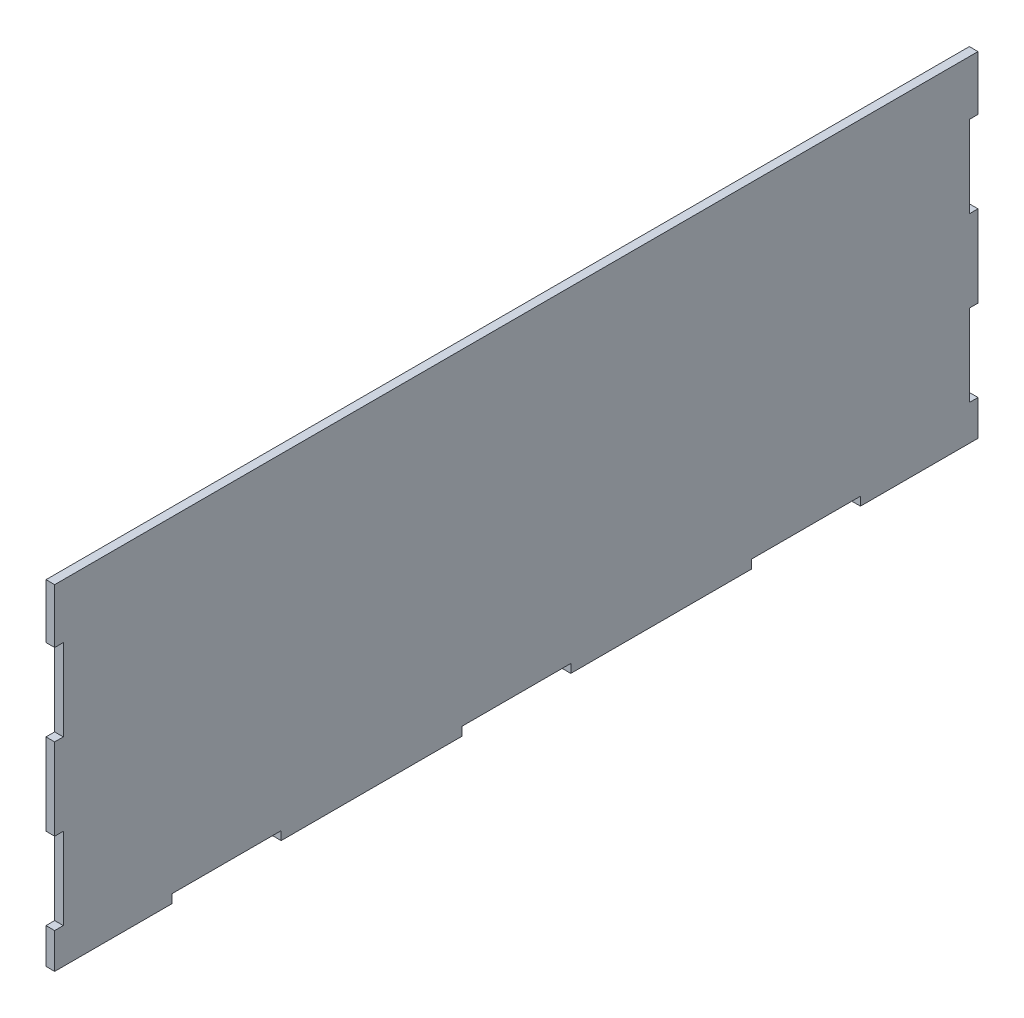
SolidWorks part; units mm, degrees
ref_plane "前视" through (0, 0, 0) normal (0, 0, 1) x (1, 0, 0)
ref_plane "上视" through (0, 0, 0) normal (0, 1, 0) x (1, 0, 0)
ref_plane "右视" through (0, 0, 0) normal (1, 0, 0) x (0, 0, -1)
sketch "Sketch1" plane through (0, 0, 0) normal (1, 0, 0) x (0, 0, -1)
  line L1 (0, 0) -> (339.05, 0)
  line L2 (0, 0) -> (0, -123)
  line L3 (0, -123) -> (339.05, -123)
  line L4 (339.05, 0) -> (339.05, -123)
  dimension "D1" = 339.05
  dimension "D2" = 123
extrude "Boss-Extrude1" add sketch "Sketch1" along normal blind 3.175
ref_axis "Axis1" through (3.175, 0, -169.525) along (0, 1, 0)
sketch "Sketch2" plane through (3.175, 0, 0) normal (1, 0, 0) x (0, 0, -1)
  line L5 (0, 0) -> (0, -123) construction
  line L6 (339.05, -123) -> (339.05, 0) construction
  line L15 (339.05, -20) -> (335.875, -20)
  line L16 (339.05, -20) -> (339.05, -50)
  line L17 (339.05, -50) -> (335.875, -50)
  line L18 (335.875, -20) -> (335.875, -50)
  line L19 (339.05, 0) -> (0, 0) construction
  line L21 (339.05, -80) -> (335.875, -80)
  line L22 (339.05, -80) -> (339.05, -110)
  line L23 (339.05, -110) -> (335.875, -110)
  line L24 (335.875, -80) -> (335.875, -110)
  line L25 (0, -20) -> (3.175, -20)
  line L26 (0, -20) -> (0, -50)
  line L27 (0, -50) -> (3.175, -50)
  line L28 (3.175, -20) -> (3.175, -50)
  line L29 (0, -80) -> (3.175, -80)
  line L30 (0, -80) -> (0, -110)
  line L31 (0, -110) -> (3.175, -110)
  line L32 (3.175, -80) -> (3.175, -110)
  dimension "D9" = 20
  dimension "D10" = 3.175
  dimension "D11" = 30
  dimension "D12" = 30
  dimension "D13" = 30
  dimension "D14" = 20
  dimension "D15" = 30
  dimension "D16" = 3.175
  dimension "D17" = 30
  dimension "D18" = 30
  dimension "D19" = 3.175
extrude "Cut-Extrude1" cut sketch "Sketch2" against normal blind 10
sketch "Sketch3" plane through (3.175, 0, 0) normal (1, 0, 0) x (0, 0, -1)
  line L0 (43.18, -123) -> (83.18, -123)
  line L1 (43.18, -123) -> (43.18, -119.825)
  line L2 (83.18, -123) -> (83.18, -119.825)
  line L3 (43.18, -119.825) -> (83.18, -119.825)
  line L4 (0, -123) -> (339.05, -123) construction
  line L10 (0, -110) -> (0, -123) construction
  dimension "D1" = 3.175
  dimension "D2" = 40
  dimension "D3" = 43.18
extrude "Cut-Extrude2" cut sketch "Sketch3" against normal through all
pattern_linear "LPattern1" count 3 spacing 106.35 along (0, 0, -1) of "Cut-Extrude2"
